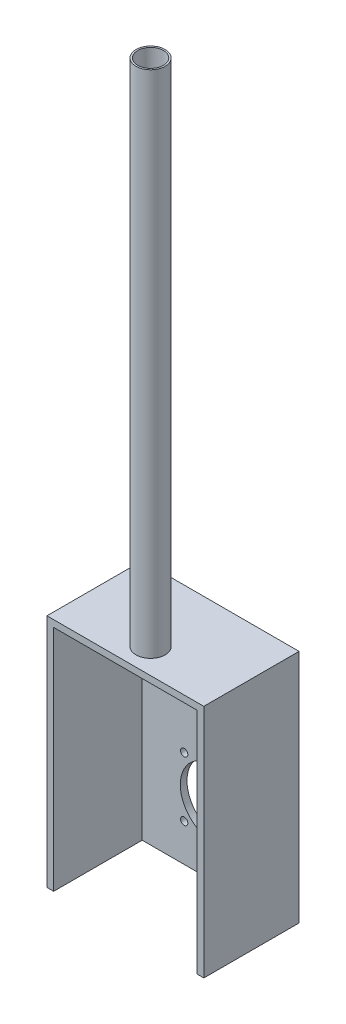
SolidWorks part; units mm, degrees
ref_plane "前视基准面" through (0, 0, 0) normal (0, 0, 1) x (1, 0, 0)
ref_plane "上视基准面" through (0, 0, 0) normal (0, 1, 0) x (1, 0, 0)
ref_plane "右视基准面" through (0, 0, 0) normal (1, 0, 0) x (0, 0, -1)
sketch "草图1" plane through (0, 0, 0) normal (0, 1, 0) x (1, 0, 0)
  circle A0 centre (0, 0) radius 13
  dimension "D1" = 26
extrude "凸台-拉伸1" add sketch "草图1" along normal blind 20
sketch "草图2" plane through (0, 20, 0) normal (0, 1, 0) x (1, 0, 0)
  circle A0 centre (0, 0) radius 13
  dimension "D1" = 26
extrude "凸台-拉伸2" add sketch "草图2" along normal blind 435
sketch "草图3" plane through (0, 455, 0) normal (0, 1, 0) x (1, 0, 0)
  circle A0 centre (0, 0) radius 11.5
  dimension "D1" = 23
sketch "草图4" plane through (0, 0, 0) normal (0, -1, 0) x (1, 0, 0)
  line L1 (-70, 22.5) -> (70, 22.5)
  line L2 (-70, 22.5) -> (-70, -62.5)
  line L3 (-70, -62.5) -> (70, -62.5)
  line L4 (70, 22.5) -> (70, -62.5)
  line L5 (-70, 22.5) -> (70, -62.5) construction
  line L6 (-70, -62.5) -> (70, 22.5) construction
  point P8 (0, -20)
  dimension "D1" = 140
  dimension "D2" = 85
  dimension "D3" = 20
extrude "凸台-拉伸3" add sketch "草图4" along normal blind 210 separate body
shell "抽壳2" thickness 6 removed face at (0, -105, 22.5)
sketch "草图5" plane through (0, 0, 22.5) normal (0, 0, 1) x (1, 0, 0)
  line L0 (70, -210) -> (-70, -210) construction
  line L1 (64, -204) -> (-64, -204)
  line L2 (64, -204) -> (64, -210)
  line L3 (64, -210) -> (-64, -210)
  line L4 (-64, -204) -> (-64, -210)
  line L5 (-64, -204) -> (-64, -6) construction
extrude "切除-拉伸3" cut sketch "草图5" against normal up to surface (79 mm away) up to face at (0, -105, -56.5)
sketch "草图6" plane through (0, 0, -62.5) normal (0, 0, -1) x (-1, 0, 0)
  line L1 (0, -150) -> (82.393, -67.607) construction
  circle A0 centre (0, -150) radius 30
  circle A1 centre (26.5165, -123.4835) radius 3.25
  circle A2 centre (26.5165, -176.5165) radius 3.25
  circle A3 centre (-26.5165, -176.5165) radius 3.25
  circle A4 centre (-26.5165, -123.4835) radius 3.25
  point P21 (0, -150)
  dimension "D1" = 60
  dimension "D5" = 6.5
  dimension "D2" = 150
  dimension "D4" = 37.5
  dimension "D6" = 4
extrude "切除-拉伸4" cut sketch "草图6" against normal blind 10
extrude "切除-拉伸5" cut sketch "草图3" against normal up to surface (461 mm away) up to face at (0, -6, -17)
